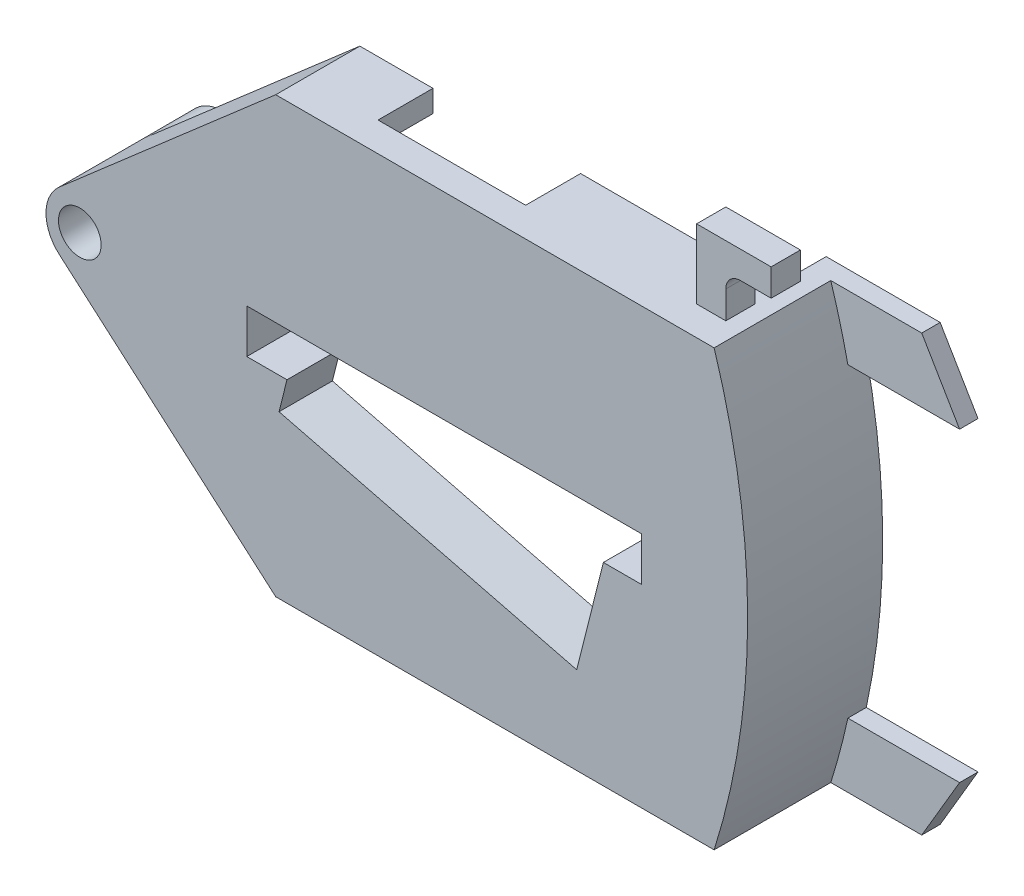
SolidWorks part; units mm, degrees
material "PW50:30:C1:0:1:2:Re:16:Tr:20:"
ref_plane "Plane1" through (0, 0, 0) normal (0, 0, 1) x (1, 0, 0)
ref_plane "Plane2" through (0, 0, 0) normal (0, 1, 0) x (1, 0, 0)
ref_plane "Plane3" through (0, 0, 0) normal (1, 0, 0) x (0, 0, -1)
sketch "Sketch1" plane through (0, 0, 0) normal (0, 0, 1) x (1, 0, 0)
  line L0 (-12.6668, 0) -> (55.8663, 0) construction
  line L1 (0, 0) -> (17.1073, 14.875)
  line L2 (0, 0) -> (17.1073, -14.875)
  line L3 (17.1073, 14.875) -> (47.1073, 14.875)
  line L4 (17.1073, -14.875) -> (47.1073, -14.875)
  arc A0 (47.1073, -14.875) -> (47.1073, 14.875) centre (0, 0) ccw
  dimension "D2" = 49.4
  dimension "D1" = 29.75
  dimension "D3" = 30
extrude "Base-Extrude" add sketch "Sketch1" along normal blind 5.76
sketch "Sketch2" plane through (0, 0, 5.76) normal (0, 0, 1) x (1, 0, 0)
  line L2 (0, 0) -> (17.1073, 14.875) construction
  line L3 (0, 0) -> (17.1073, -14.875) construction
  circle A0 centre (4.0387, 0) radius 2.65
  dimension "D1" = 5.3
extrude "Boss-Extrude1" add sketch "Sketch2" against normal blind 9.45
sketch "Sketch3" plane through (0, 0, 5.76) normal (0, 0, 1) x (1, 0, 0)
  line L0 (0, 0) -> (17.1073, -14.875) construction
  line L1 (0, 0) -> (17.1073, 14.875) construction
  line L2 (0, 0) -> (2.2999, -1.9998)
  line L3 (0, 0) -> (2.2999, 1.9998)
  arc A0 (2.2999, 1.9998) -> (2.2999, -1.9998) centre (4.0387, 0) ccw construction
  arc A1 (2.2999, 1.9998) -> (2.2999, -1.9998) centre (4.0387, 0) ccw
extrude "Cut-Extrude3" cut sketch "Sketch3" against normal through all
sketch "Sketch4" plane through (0, 0, -3.69) normal (0, 0, -1) x (-1, 0, 0)
  circle A0 centre (-4.0387, 0) radius 1.37
  dimension "D1" = 2.74
extrude "Boss-Extrude2" add sketch "Sketch4" along normal blind 2.64 draft 1 draft outward yes
sketch "Sketch6" plane through (0, 0, 5.76) normal (0, 0, 1) x (1, 0, 0)
  line L0 (1.3887, 0) -> (49.4, 0) construction
  line L1 (1.3887, 0) -> (1.3887, 1.0249) construction
  arc A1 (47.1073, -14.875) -> (47.1073, 14.875) centre (0, 0) ccw construction
  arc A2 (2.2999, 1.9998) -> (2.2999, -1.9998) centre (4.0387, 0) ccw construction
  dimension "D1" = 48.0113
sketch "Sketch7" plane through (0, 0, 5.76) normal (0, 0, 1) x (1, 0, 0)
  circle A2 centre (3.7016, 0) radius 1.15
  dimension "D1" = 2.3
extrude "Cut-Extrude4" cut sketch "Sketch7" against normal offset from surface (11.09 mm away) 1 up to face at (2.6226, 0, -6.33)
sketch "Sketch8" plane through (0, 0, 5.76) normal (0, 0, 1) x (1, 0, 0)
  line L0 (-0.719, 1.37) -> (50.999, 1.37) construction
  line L1 (15.1282, 1.37) -> (42.1282, 1.37)
  line L2 (42.1282, 1.37) -> (42.1282, -1.63)
  line L3 (42.1282, -1.63) -> (39.5282, -1.63)
  line L4 (39.5282, -1.63) -> (37.7042, -8.9048)
  line L5 (37.7042, -8.9048) -> (17.3347, -3.7977)
  line L6 (17.3347, -3.7977) -> (17.8782, -1.63)
  line L7 (17.8782, -1.63) -> (15.1282, -1.63)
  line L8 (15.1282, -1.63) -> (15.1282, 1.37)
  circle A0 centre (4.0387, 0) radius 1.37 construction
  dimension "D1" = 27
  dimension "D2" = 21
  dimension "D3" = 3
  dimension "D4" = 3
  dimension "D5" = 7.5
  dimension "D6" = 2.6
  dimension "D7" = 2.75
  dimension "D8" = 2.2348
extrude "Cut-Extrude5" cut sketch "Sketch8" against normal through all
sketch "Sketch9" plane through (0, 0, 0) normal (0, 0, -1) x (-1, 0, 0)
  line L12 (-3.2841, 0.8678) -> (-17.6682, 13.375)
  line L13 (-17.6682, 13.375) -> (-45.9948, 13.375)
  line L14 (-17.6682, -13.375) -> (-45.9948, -13.375)
  line L15 (-3.2841, -0.8678) -> (-17.6682, -13.375)
  line L16 (-5.0857, 2.4344) -> (-17.6682, 13.375)
  line L17 (-17.6682, 13.375) -> (-45.9948, 13.375)
  line L18 (-17.6682, -13.375) -> (-45.9948, -13.375)
  line L19 (-5.0857, -2.4344) -> (-17.6682, -13.375)
  circle A4 centre (-4.0387, 0) radius 2.65 construction
  arc A5 (-45.9948, 13.375) -> (-45.9948, -13.375) centre (0, 0) ccw
  arc A6 (-45.9948, 13.375) -> (-45.9948, -13.375) centre (0, 0) ccw
  arc A7 (-5.0857, 2.4344) -> (-5.0857, -2.4344) centre (-4.0387, 0) ccw
  dimension "D1" = 1.5
extrude "Cut-Extrude6" cut sketch "Sketch9" against normal offset from surface (3.76 mm away) 2 up to face at (4.8516, 0, 5.76)
sketch "Sketch10" plane through (0, 0, 3.76) normal (0, 0, -1) x (-1, 0, 0)
  line L0 (-15.1282, 1.37) -> (-15.1282, -1.63) construction
  line L1 (-15.1282, -1.63) -> (-17.8782, -1.63) construction
  line L2 (-17.8782, -1.63) -> (-17.3347, -3.7977) construction
  line L3 (-17.3347, -3.7977) -> (-37.7042, -8.9048) construction
  line L4 (-37.7042, -8.9048) -> (-39.5282, -1.63) construction
  line L5 (-39.5282, -1.63) -> (-42.1282, -1.63) construction
  line L6 (-42.1282, -1.63) -> (-42.1282, 1.37) construction
  line L7 (-42.1282, 1.37) -> (-15.1282, 1.37) construction
  line L8 (-43.1282, -2.63) -> (-43.1282, 2.37)
  line L9 (-40.3084, -2.63) -> (-43.1282, -2.63)
  line L10 (-38.431, -10.118) -> (-40.3084, -2.63)
  line L11 (-16.1215, -4.5245) -> (-38.431, -10.118)
  line L12 (-16.5965, -2.63) -> (-16.1215, -4.5245)
  line L13 (-14.1282, -2.63) -> (-16.5965, -2.63)
  line L14 (-14.1282, 2.37) -> (-14.1282, -2.63)
  line L15 (-43.1282, 2.37) -> (-14.1282, 2.37)
  line L16 (-43.1282, -2.63) -> (-43.1282, 2.37)
  line L17 (-40.3084, -2.63) -> (-43.1282, -2.63)
  line L18 (-38.431, -10.118) -> (-40.3084, -2.63)
  line L19 (-16.1215, -4.5245) -> (-38.431, -10.118)
  line L20 (-16.5965, -2.63) -> (-16.1215, -4.5245)
  line L21 (-14.1282, -2.63) -> (-16.5965, -2.63)
  line L22 (-14.1282, 2.37) -> (-14.1282, -2.63)
  line L23 (-43.1282, 2.37) -> (-14.1282, 2.37)
  line L24 (-15.1282, 1.37) -> (-15.1282, -1.63)
  line L25 (-15.1282, -1.63) -> (-17.8782, -1.63)
  line L26 (-17.8782, -1.63) -> (-17.3347, -3.7977)
  line L27 (-17.3347, -3.7977) -> (-37.7042, -8.9048)
  line L28 (-37.7042, -8.9048) -> (-39.5282, -1.63)
  line L29 (-39.5282, -1.63) -> (-42.1282, -1.63)
  line L30 (-42.1282, -1.63) -> (-42.1282, 1.37)
  line L31 (-42.1282, 1.37) -> (-15.1282, 1.37)
  dimension "D1" = 1
extrude "Boss-Extrude3" add sketch "Sketch10" along normal blind 1.65
sketch "Sketch11" plane through (0, 14.875, 0) normal (0, 1, 0) x (-1, 0, 0)
  line L0 (-32.2073, 0) -> (-22.1073, 0)
  line L1 (-32.2073, 0) -> (-32.2073, 3.76)
  line L2 (-22.1073, 3.76) -> (-32.2073, 3.76)
  line L3 (-22.1073, 3.76) -> (-22.1073, 0)
  line L4 (-17.1073, 0) -> (-47.1073, 0) construction
  line L5 (-17.1073, 5.76) -> (-17.1073, 0) construction
  line L6 (-17.6682, 3.76) -> (-45.9948, 3.76) construction
  dimension "D1" = 5
  dimension "D2" = 10.1
extrude "Cut-Extrude7" cut sketch "Sketch11" against normal up to surface (1.5 mm away) up to face at (31.8315, 13.375, 1.88)
sketch "Sketch12" plane through (0, -14.875, 0) normal (0, -1, 0) x (1, 0, 0)
  line L0 (22.1073, 0) -> (22.1073, 3.76) construction
  line L1 (32.2073, 3.76) -> (32.2073, 0) construction
  line L2 (22.1073, 0) -> (22.1073, 1.65)
  line L3 (32.2073, 1.65) -> (32.2073, 0)
  line L4 (32.2073, 1.65) -> (22.1073, 1.65)
  line L5 (32.2073, 0) -> (22.1073, 0)
  dimension "D1" = 1.65
extrude "Cut-Extrude8" cut sketch "Sketch12" against normal up to surface (1.5 mm away) up to face at (31.8315, -13.375, 1.88)
sketch "Sketch13" plane through (0, 0, 3.76) normal (0, 0, -1) x (-1, 0, 0)
  line L4 (-17.6682, -13.375) -> (-17.6682, -9.095) construction
  line L5 (-18.3782, -13.375) -> (-18.3782, -9.095)
  line L6 (-17.6682, -13.375) -> (-22.1073, -13.375) construction
  line L7 (-18.3782, -9.095) -> (-16.9582, -9.095)
  line L8 (-16.9582, -9.095) -> (-16.9582, -12.7576)
  line L9 (-5.0857, -2.4344) -> (-17.6682, -13.375) construction
  line L10 (-16.9582, -12.7576) -> (-17.6682, -13.375)
  line L11 (-17.6682, -13.375) -> (-18.3782, -13.375)
  dimension "D1" = 1.42
  dimension "D2" = 4.28
extrude "Boss-Extrude4" add sketch "Sketch13" along normal up to surface (3.76 mm away) up to face at (14.3855, -10.2226, 0)
fillet "Fillet1" radius 0.7 2 edges at (18.3782, -9.095, 1.88) (16.9582, -9.095, 1.88)
sketch "Sketch14" plane through (0, 0, 0) normal (0, 0, -1) x (-1, 0, 0)
  line L1 (-38.431, -10.118) -> (-38.431, -18.0474) construction
  line L2 (-38.431, -10.675) -> (-39.801, -10.675)
  line L3 (-39.801, -10.675) -> (-39.801, -13.375)
  line L4 (-32.2073, -13.375) -> (-45.9948, -13.375) construction
  line L5 (-39.801, -13.375) -> (-45.9948, -13.375)
  line L6 (-45.9948, -13.375) -> (-47.1073, -14.875)
  line L7 (-47.1073, -14.875) -> (-38.431, -14.875)
  line L8 (-38.431, -14.875) -> (-38.431, -10.675)
  dimension "D1" = 4.2
  dimension "D2" = 1.37
extrude "Boss-Extrude5" add sketch "Sketch14" along normal blind 1.42 and the other way up to surface (3.76 mm away) other way up to face at (28.2463, -2.5528, 3.76)
fillet "Fillet5" radius 0.685 2 edges at (38.431, -10.675, 1.17) (39.801, -10.675, 1.17)
sketch "Sketch15" plane through (0, 0, 0) normal (0, 0, -1) x (-1, 0, 0)
  line L2 (-47.1073, 14.875) -> (-45.5318, 14.875)
  line L4 (-47.1073, -14.875) -> (-45.5318, -14.875)
  arc A0 (-45.9948, 13.375) -> (-45.9948, -13.375) centre (0, 0) ccw construction
  arc A1 (-47.1073, 14.875) -> (-47.1073, -14.875) centre (0, 0) ccw construction
  arc A2 (-45.5318, 14.875) -> (-45.5318, -14.875) centre (0, 0) ccw
  arc A3 (-47.1073, 14.875) -> (-47.1073, -14.875) centre (0, 0) ccw
extrude "Boss-Extrude6" add sketch "Sketch15" along normal blind 3.48
sketch "Sketch16" plane through (0, 0, -3.48) normal (0, 0, -1) x (-1, 0, 0)
  line L0 (-47.1073, -14.875) -> (-45.5318, -14.875) construction
  line L1 (-47.1073, 14.875) -> (-45.5318, 14.875) construction
  line L2 (-47.1073, -14.875) -> (-45.5318, -14.875)
  line L3 (-47.1073, 14.875) -> (-45.5318, 14.875)
  line L4 (0, 0) -> (-58.7476, 0) construction
  line L5 (-47.1073, 14.875) -> (-53.3318, 14.875)
  line L6 (-47.1073, -14.875) -> (-53.3318, -14.875)
  line L7 (-53.3318, 14.875) -> (-55.9216, 10.4705)
  line L8 (-53.3318, -14.875) -> (-55.9216, -10.4705)
  line L9 (-55.9216, 10.4705) -> (-46.7416, 10.4705)
  line L10 (-55.9216, -10.4705) -> (-46.7416, -10.4705)
  arc A0 (-45.5318, 14.875) -> (-45.5318, -14.875) centre (0, 0) ccw construction
  arc A1 (-45.5318, 14.875) -> (-46.7416, 10.4705) centre (0, 0) ccw
  arc A3 (-46.7416, -10.4705) -> (-45.5318, -14.875) centre (0, 0) ccw
  dimension "D1" = 7.8
  dimension "D2" = 9.18
extrude "Boss-Extrude7" add sketch "Sketch16" against normal blind 1.26
sketch "Sketch17" plane through (0, 0, 5.76) normal (0, 0, 1) x (1, 0, 0)
  line L0 (45.9073, 14.875) -> (45.9073, 17.765)
  line L1 (17.1073, 14.875) -> (47.1073, 14.875) construction
  line L2 (45.9073, 17.765) -> (49.0073, 17.765)
  line L3 (49.0073, 17.765) -> (49.0073, 19.625)
  line L4 (49.0073, 19.625) -> (43.9073, 19.625)
  line L5 (43.9073, 19.625) -> (43.9073, 14.875)
  line L6 (43.9073, 14.875) -> (45.9073, 14.875)
  dimension "D1" = 5.1
  dimension "D2" = 1.86
  dimension "D3" = 4.75
  dimension "D4" = 2
  dimension "D5" = 1.2
extrude "Boss-Extrude8" add sketch "Sketch17" against normal blind 4
sketch "Sketch18" plane through (43.9073, 0, 0) normal (-1, 0, 0) x (0, 0, 1)
  line L0 (3.76, 19.625) -> (3.76, 13.375) construction
  line L1 (3.76, 19.625) -> (3.76, 14.875)
  line L4 (5.76, 14.875) -> (5.76, 19.625)
  line L5 (5.76, 19.625) -> (1.76, 19.625)
  line L6 (1.76, 19.625) -> (1.76, 14.875)
  line L7 (1.76, 14.875) -> (5.76, 14.875)
  line L8 (5.76, 14.875) -> (5.76, 19.625)
  line L9 (5.76, 19.625) -> (3.76, 19.625)
  line L11 (3.76, 14.875) -> (5.76, 14.875)
  dimension "D1" = 0
extrude "Cut-Extrude9" cut sketch "Sketch18" against normal through all
fillet "Fillet2" radius 1 1 edges at (45.9073, 17.765, 2.76)
sketch "Sketch21" plane through (0, 0, 1.18) normal (0, 0, -1) x (-1, 0, 0)
  circle A0 centre (-3.7016, 0) radius 1.46 construction
  circle A1 centre (-3.7016, 0) radius 1.46
extrude "Cut-Extrude13" cut sketch "Sketch21" against normal up to surface (4.58 mm away) up to face at (22.4017, 0, 5.76)
